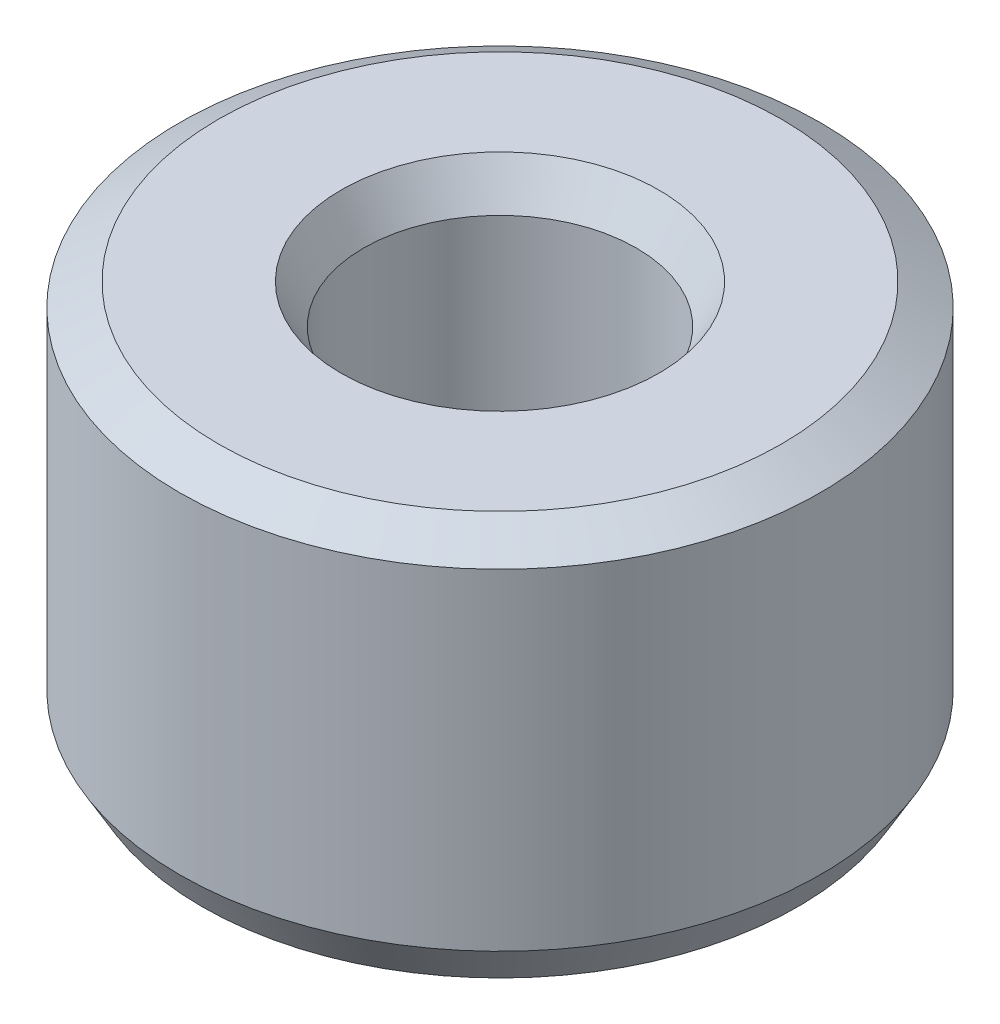
SolidWorks part; units mm, degrees
ref_plane "Front Plane" through (0, 0, 0) normal (0, 0, 1) x (1, 0, 0)
ref_plane "Top Plane" through (0, 0, 0) normal (0, 1, 0) x (1, 0, 0)
ref_plane "Right Plane" through (0, 0, 0) normal (1, 0, 0) x (0, 0, -1)
sketch "Sketch1" plane through (0, 0, 0) normal (0, 1, 0) x (1, 0, 0)
  circle A0 centre (0, 0) radius 30
  dimension "SLEEVE_OD" = 60
extrude "Boss-Extrude1" add sketch "Sketch1" along normal blind 36.7363
sketch "Sketch2" plane through (0, 0, 0) normal (0, 1, 0) x (1, 0, 0)
  circle A0 centre (0, 0) radius 12.7616
  dimension "BORE_D" = 25.5232
extrude "Cut-Extrude1" cut sketch "Sketch2" along normal through all
chamfer "Chamfer1" distance 2.109 angle 60 4 edges at (0, 36.7363, 12.7616) (0, 0, 12.7616) (0, 0, 30) (0, 36.7363, 30) first distance on face at (0, 36.7363, 12.7616) first distance on face at (0, 0, 12.7616) first distance on face at (0, 36.7363, 30)
